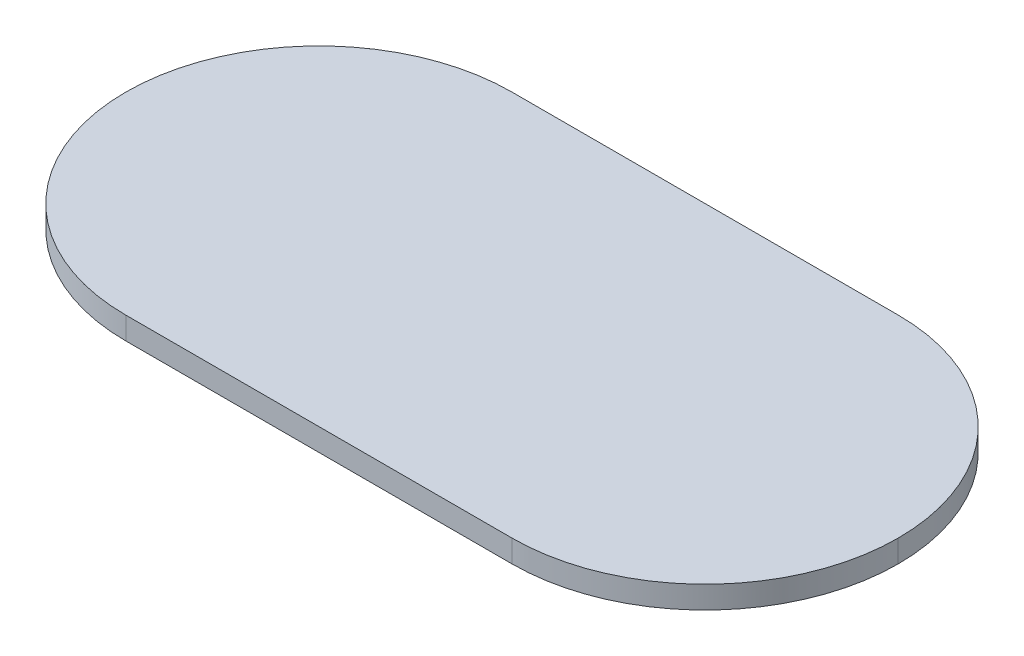
SolidWorks part; units mm, degrees
ref_plane "Front" through (0, 0, 0) normal (0, 0, 1) x (1, 0, 0)
ref_plane "Top" through (0, 0, 0) normal (0, 1, 0) x (1, 0, 0)
ref_plane "Right" through (0, 0, 0) normal (1, 0, 0) x (0, 0, -1)
sketch "Sketch1" plane through (0, 0, 0) normal (0, 1, 0) x (1, 0, 0)
  line L1 (-69, -34.5) -> (69, -34.5)
  line L2 (-69, -34.5) -> (-69, 34.5)
  line L3 (-69, 34.5) -> (69, 34.5)
  line L4 (69, -34.5) -> (69, 34.5)
  line L5 (-69, -34.5) -> (69, 34.5) construction
  line L6 (-69, 34.5) -> (69, -34.5) construction
  point P0 (0, 0)
  dimension "D1" = 69
  dimension "D2" = 138
extrude "Boss-Extrude1" add sketch "Sketch1" along normal blind 4
fillet "Fillet1" radius 34.5 4 edges at (69, 2, 34.5) (69, 2, -34.5) (-69, 2, -34.5) (-69, 2, 34.5)
